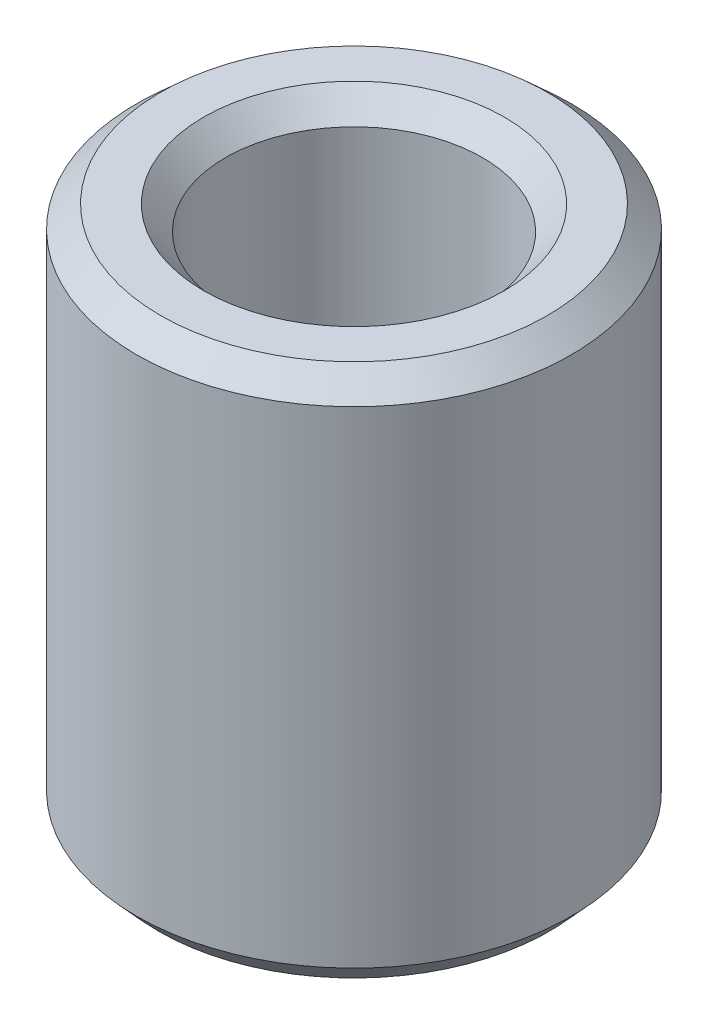
SolidWorks part; units mm, degrees
ref_plane "Front Plane" through (0, 0, 0) normal (0, 0, 1) x (1, 0, 0)
ref_plane "Top Plane" through (0, 0, 0) normal (0, 1, 0) x (1, 0, 0)
ref_plane "Right Plane" through (0, 0, 0) normal (1, 0, 0) x (0, 0, -1)
sketch "Sketch1" plane through (0, 0, 0) normal (0, 1, 0) x (1, 0, 0)
  circle A0 centre (0, 0) radius 37.5
  dimension "SLEEVE_OD" = 75
extrude "Boss-Extrude1" add sketch "Sketch1" along normal blind 91.7811
sketch "Sketch2" plane through (0, 0, 0) normal (0, 1, 0) x (1, 0, 0)
  circle A0 centre (0, 0) radius 22.1505
  dimension "BORE_D" = 44.301
extrude "Cut-Extrude1" cut sketch "Sketch2" along normal through all
chamfer "Chamfer1" distance 3.783 angle 47.619 4 edges at (0, 91.7811, 22.1505) (0, 0, 22.1505) (0, 0, 37.5) (0, 91.7811, 37.5) first distance on face at (0, 91.7811, 22.1505) first distance on face at (0, 0, 22.1505) first distance on face at (0, 91.7811, 37.5)
